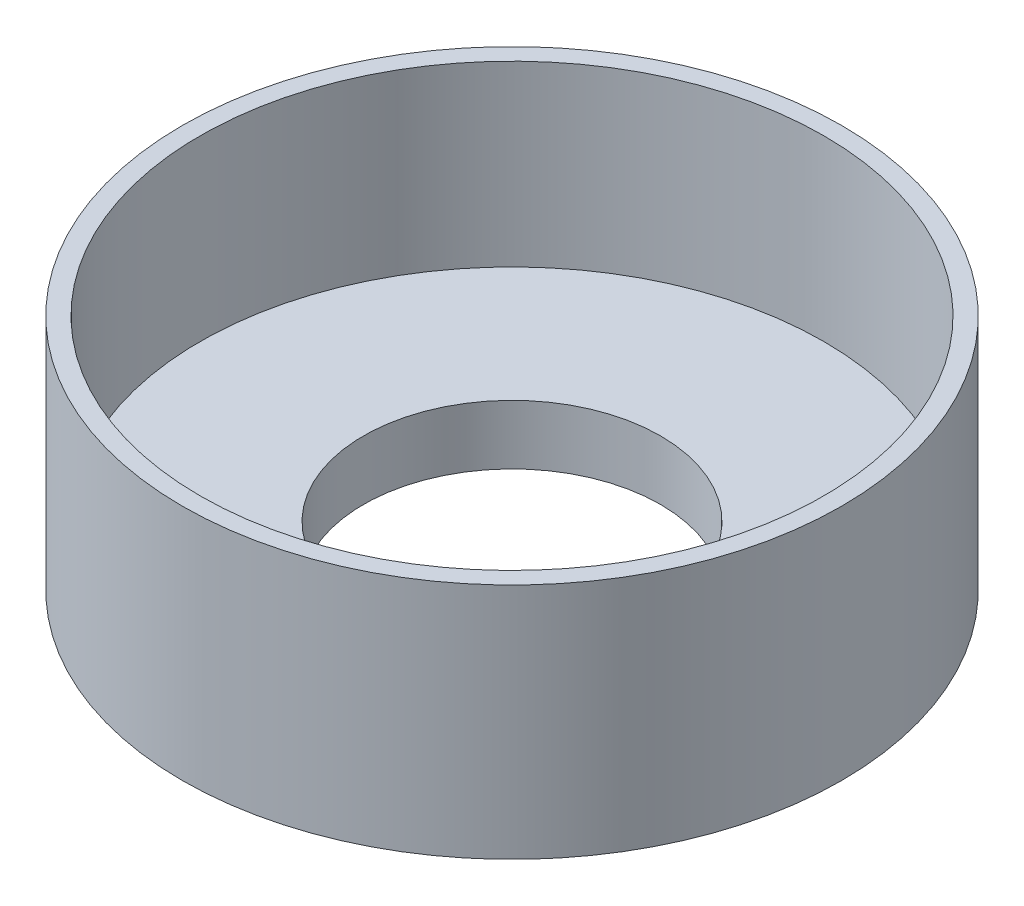
SolidWorks part; units mm, degrees
ref_plane "Front Plane" through (0, 0, 0) normal (0, 0, 1) x (1, 0, 0)
ref_plane "Top Plane" through (0, 0, 0) normal (0, 1, 0) x (1, 0, 0)
ref_plane "Right Plane" through (0, 0, 0) normal (1, 0, 0) x (0, 0, -1)
sketch "Sketch1" plane through (0, 0, 0) normal (0, 1, 0) x (1, 0, 0)
  circle A2 centre (0, 0) radius 5
  circle A3 centre (0, 0) radius 11.1
  dimension "D1" = 22.2
  dimension "D2" = 10
extrude "Boss-Extrude1" add sketch "Sketch1" along normal blind 2
sketch "Sketch2" plane through (0, 2, 0) normal (0, 1, 0) x (1, 0, 0)
  circle A0 centre (0, 0) radius 10.5
  circle A1 centre (0, 0) radius 11.1
  dimension "D1" = 0.6
  dimension "D2" = 22.2
extrude "Boss-Extrude2" add sketch "Sketch2" along normal blind 6
